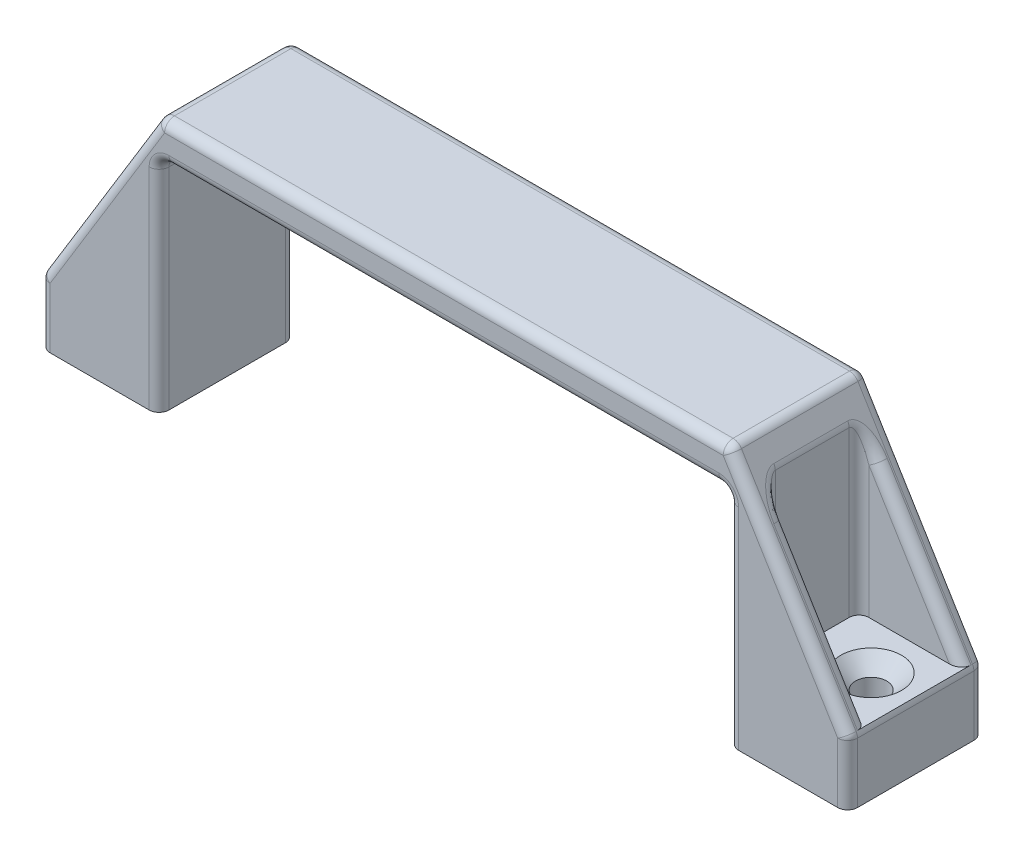
SolidWorks part; units mm, degrees
material "ABS"
ref_plane "Přední rovina" through (0, 0, 0) normal (0, 0, 1) x (1, 0, 0)
ref_plane "Horní rovina" through (0, 0, 0) normal (0, 1, 0) x (1, 0, 0)
ref_plane "Pravá rovina" through (0, 0, 0) normal (1, 0, 0) x (0, 0, -1)
sketch "Skica1" plane through (0, 0, 0) normal (0, 0, 1) x (1, 0, 0)
  line L0 (-60.9746, 0) -> (-36.9746, 0)
  line L1 (-60.9746, 0) -> (-60.9746, 12.1376)
  line L2 (-60.6815, 13.18) -> (-37.5594, 51.0424)
  line L3 (-35.8525, 52) -> (76.9034, 52)
  line L4 (78.6102, 51.0424) -> (101.7323, 13.18)
  line L5 (102.0254, 12.1376) -> (102.0254, 0)
  line L6 (-36.9746, 42.5) -> (-36.9746, 0)
  line L7 (-34.9746, 44.5) -> (76.0254, 44.5)
  line L8 (78.0254, 42.5) -> (78.0254, 0)
  line L9 (78.0254, 0) -> (102.0254, 0)
  arc A0 (-34.9746, 44.5) -> (-36.9746, 42.5) centre (-34.9746, 42.5) ccw
  arc A1 (-35.8525, 52) -> (-37.5594, 51.0424) centre (-35.8525, 50) ccw
  arc A2 (78.6102, 51.0424) -> (76.9034, 52) centre (76.9034, 50) ccw
  arc A3 (78.0254, 42.5) -> (76.0254, 44.5) centre (76.0254, 42.5) ccw
  arc A4 (102.0254, 12.1376) -> (101.7323, 13.18) centre (100.0254, 12.1376) ccw
  arc A5 (-60.9746, 12.1376) -> (-60.6815, 13.18) centre (-58.9746, 12.1376) cw
  point P13 (-36.9746, 44.5)
  point P16 (-36.9746, 52)
  point P19 (78.0254, 52)
  point P22 (78.0254, 44.5)
  point P25 (102.0254, 12.7)
  point P28 (-60.9746, 12.7)
  dimension "D8" = 2
  dimension "D1" = 163
  dimension "D2" = 24
  dimension "D3" = 24
  dimension "D4" = 44.5
  dimension "D5" = 52
  dimension "D6" = 12.7
  dimension "D7" = 12.7
extrude "Vysunout1" add sketch "Skica1" along normal blind 27.5
sketch "Skica3" plane through (102.0254, 0, 0) normal (1, 0, 0) x (0, 0, -1)
  line L0 (-27.5, 13.18) -> (0, 13.18) construction
  line L1 (-23.2, 13.18) -> (-4.3, 13.18)
  line L2 (-23.2, 13.18) -> (-23.2, 51.0424)
  line L3 (-23.2, 51.0424) -> (-4.3, 51.0424)
  line L4 (-4.3, 13.18) -> (-4.3, 51.0424)
  line L5 (-27.5, 51.0424) -> (0, 51.0424) construction
  line L6 (0, 13.18) -> (0, 51.0424) construction
  line L7 (-27.5, 13.18) -> (-27.5, 51.0424) construction
  dimension "D1" = 4.3
  dimension "D2" = 4.3
extrude "Odebrat vysunutím1" cut sketch "Skica3" against normal blind 20.9
sketch "Skica4" plane through (-60.9746, 0, 0) normal (-1, 0, 0) x (0, 0, 1)
  line L0 (27.5, 13.18) -> (0, 13.18) construction
  line L1 (4.3, 13.18) -> (23.2, 13.18)
  line L2 (4.3, 13.18) -> (4.3, 51.0424)
  line L3 (4.3, 51.0424) -> (23.2, 51.0424)
  line L4 (23.2, 13.18) -> (23.2, 51.0424)
  line L5 (27.5, 51.0424) -> (0, 51.0424) construction
  line L6 (0, 51.0424) -> (0, 13.18) construction
  line L7 (27.5, 51.0424) -> (27.5, 13.18) construction
  dimension "D1" = 4.3
  dimension "D2" = 4.3
extrude "Odebrat vysunutím2" cut sketch "Skica4" against normal blind 20.9
sketch "Skica5" plane through (0, 13.18, 0) normal (0, 1, 0) x (-1, 0, 0)
  line L0 (-101.7323, 13.75) -> (60.6815, 13.75) construction
  line L1 (-101.7323, 23.2) -> (-101.7323, 4.3) construction
  line L2 (60.6815, 23.2) -> (60.6815, 4.3) construction
  line L3 (51.9746, 6.3) -> (51.9746, 21.2) construction
  line L4 (-93.0254, 6.3) -> (-93.0254, 21.2) construction
  line L5 (-81.1254, 4.3) -> (-101.7323, 4.3) construction
  line L6 (-81.1254, 23.2) -> (-101.7323, 23.2) construction
  line L7 (40.0746, 4.3) -> (60.6815, 4.3) construction
  line L8 (40.0746, 23.2) -> (60.6815, 23.2) construction
  line L9 (60.9746, 27.5) -> (60.9746, 0) construction
  line L10 (-102.0254, 27.5) -> (-102.0254, 0) construction
  circle A0 centre (-93.0254, 13.75) radius 3.15
  circle A1 centre (51.9746, 13.75) radius 3.15
  dimension "D8" = 6.3
  dimension "D9" = 6.3
  dimension "D1" = 2
  dimension "D2" = 2
  dimension "D3" = 2
  dimension "D4" = 2
  dimension "D5" = 145
  dimension "D6" = 9
  dimension "D7" = 9
extrude "Odebrat vysunutím3" cut sketch "Skica5" against normal through all
chamfer "Zkosit1" distance 3 angle 45 2 edges at (-51.9746, 13.18, 16.9) (93.0254, 13.18, 16.9)
fillet "Zaoblit1" radius 2 28 edges at (-36.9746, 21.25, 0) (-36.3888, 43.9142, 0) (78.0254, 21.25, 0) (77.4396, 43.9142, 0) (78.0254, 21.25, 27.5) (77.4396, 43.9142, 27.5) (20.5254, 44.5, 27.5) (-36.3888, 43.9142, 27.5) (102.0254, 6.0688, 27.5) (101.9508, 12.679, 27.5) (90.1713, 32.1112, 27.5) (77.8819, 51.7442, 27.5) (-60.9746, 6.0688, 27.5) (-60.8999, 12.679, 27.5) (-49.1204, 32.1112, 27.5) (-36.8311, 51.7442, 27.5) (102.0254, 6.0688, 0) (101.9508, 12.679, 0) (90.1713, 32.1112, 0) (77.8819, 51.7442, 0) (-60.9746, 6.0688, 0) (-60.8999, 12.679, 0) (-49.1204, 32.1112, 0) (-36.8311, 51.7442, 0) (20.5254, 44.5, 0) (-36.9746, 21.25, 27.5) (20.5254, 52, 27.5) (20.5254, 52, 0)
fillet "Zaoblit2" radius 2 10 edges at (81.1254, 46.9238, 13.75) (91.4289, 30.0519, 23.2) (91.4289, 30.0519, 4.3) (81.1254, 30.0519, 4.3) (81.1254, 30.0519, 23.2) (-40.0746, 30.0519, 4.3) (-40.0746, 30.0519, 23.2) (-50.378, 30.0519, 23.2) (-40.0746, 46.9238, 13.75) (-50.378, 30.0519, 4.3)
